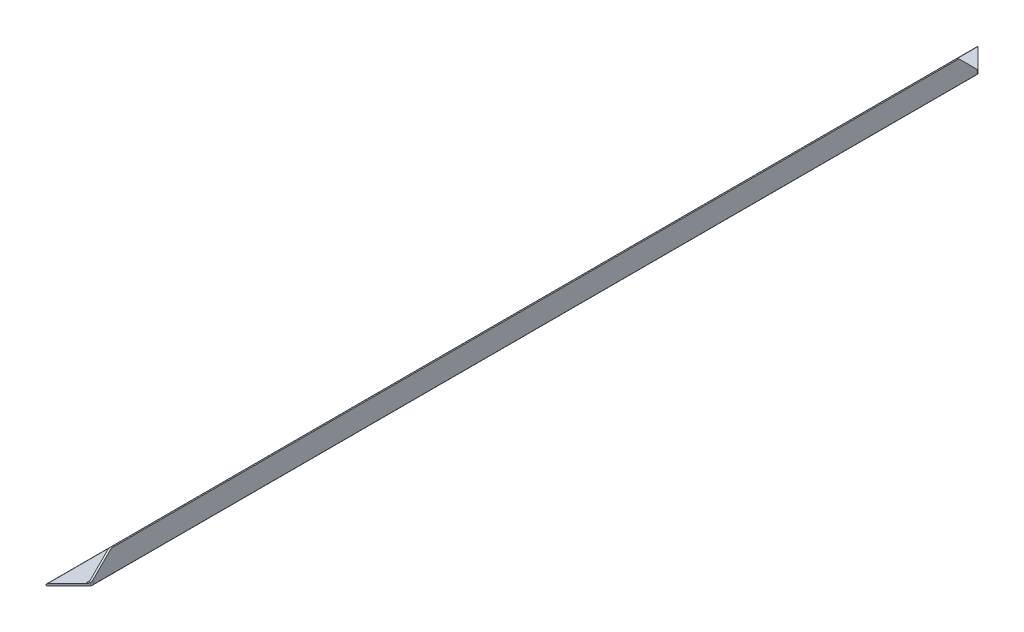
SolidWorks part; units mm, degrees
ref_plane "Front Plane" through (0, 0, 0) normal (0, 0, 1) x (1, 0, 0)
ref_plane "Top Plane" through (0, 0, 0) normal (0, 1, 0) x (1, 0, 0)
ref_plane "Right Plane" through (0, 0, 0) normal (1, 0, 0) x (0, 0, -1)
sketch "Sketch1" plane through (0, 0, 0) normal (0, 0, 1) x (1, 0, 0)
  line L0 (-3, 6) -> (-3, 35)
  line L1 (-1, 0) -> (-35, 0)
  line L2 (0, 1) -> (0, 35)
  line L3 (0, 35) -> (-35, 35) construction
  line L4 (-35, 0) -> (-35, 35) construction
  line L5 (0, 0) -> (-35, 35) construction
  line L6 (0, 35) -> (-35, 0) construction
  line L7 (0, 0) -> (-3, 0) construction
  line L8 (0, 0) -> (0, 3) construction
  line L9 (0, 3) -> (-3, 3) construction
  line L10 (-3, 0) -> (-3, 3) construction
  line L11 (0, 0) -> (-3, 3) construction
  line L12 (0, 3) -> (-3, 0) construction
  line L13 (-3, 35) -> (0, 35)
  line L14 (-6, 3) -> (-35, 3)
  line L15 (-35, 3) -> (-35, 0)
  line L16 (-35, 0) -> (-35.3886, -0.0241)
  arc A0 (-3, 6) -> (-6, 3) centre (-6, 6) cw
  arc A1 (-1, 0) -> (0, 1) centre (-1, 1) ccw
  point P5 (-17.5, 17.5)
  point P9 (-1.5, 1.5)
  dimension "D3" = 3
  dimension "D4" = 1
  dimension "D1" = 3
  dimension "D2" = 35
extrude "Boss-Extrude1" add sketch "Sketch1" along normal mid plane 1412 contours L1 A1 L2 L13 L0 A0 L14 L15
fillet "Fillet1" radius 1.5 2 edges at (-35, 3, 0) (-3, 35, 0)
sketch "Sketch2" plane through (0, 0, 0) normal (0, -1, 0) x (1, 0, 0)
  line L0 (-35, -706) -> (0, -671)
  line L2 (0, 706) -> (0, -706) construction
  line L3 (0, -671) -> (0, -706)
  line L4 (0, -706) -> (-35, -706)
  dimension "D1" = 45
extrude "Cut-Extrude1" cut sketch "Sketch2" against normal through all
sketch "Sketch3" plane through (0, 0, 0) normal (1, 0, 0) x (0, 0, -1)
  line L0 (642, 35) -> (674, 3)
  line L2 (-706, 35) -> (671, 35) construction
  line L3 (677, 3) -> (704.5, 3) construction
  line L4 (674, 3) -> (706, 3)
  line L5 (706, 1.5) -> (706, 0) construction
  line L6 (706, 3) -> (674, 35)
  line L7 (674, 6) -> (674, 33.5) construction
  line L9 (674, 35) -> (642, 35)
  dimension "D1" = 45
extrude "Cut-Extrude2" cut sketch "Sketch3" against normal blind 10
mirror "Mirror1" about plane through (0, 0, 0) normal (0, 0, 1) of "Cut-Extrude2", "Cut-Extrude1"
fillet "Fillet2" radius 4 1 edges at (-0.75, 35, -642)
fillet "Fillet3" radius 4 2 edges at (-0.2929, 0.2929, -671.2929) (0, 3.5, -671)
fillet "Fillet4" radius 4 2 edges at (0, 3.5, 671) (-0.2929, 0.2929, 671.2929)
fillet "Fillet5" radius 4 1 edges at (-0.75, 35, 642)
sketch "Sketch4" plane through (-35, 0, 0) normal (-1, 0, 0) x (0, 0, 1)
  line L0 (706, 1.5) -> (-706, 1.5) construction
  line L1 (711.148, -1.5) -> (700.8769, -1.5) construction
  line L2 (711.148, -1.5) -> (711.148, 1.5) construction
  line L3 (711.148, 1.5) -> (700.8769, 1.5) construction
  line L4 (700.8769, -1.5) -> (700.8769, 1.5) construction
  line L5 (706, 0) -> (-706, 0) construction
  line L7 (711.148, 1.5) -> (706, 1.5)
  line L8 (706, 1.5) -> (706, 1)
  line L9 (705, 0) -> (700.8769, 0)
  line L10 (700.8769, 0) -> (700.8769, -1.5)
  line L11 (700.8769, -1.5) -> (711.148, -1.5)
  line L12 (711.148, -1.5) -> (711.148, 1.5)
  arc A0 (706, 1) -> (705, 0) centre (705, 1) cw
  line M7 (706, 0) -> (706, 1.5)
  line M10 (-706, 0) -> (706, 0)
  dimension "D1" = 1
extrude "Cut-Extrude3" cut sketch "Sketch4" against normal blind 10 contours L11 L12 L7 L10 M7 M10 | A0 M7 M10
mirror "Mirror2" about plane through (0, 0, 0) normal (0, 0, 1) of "Cut-Extrude3"
